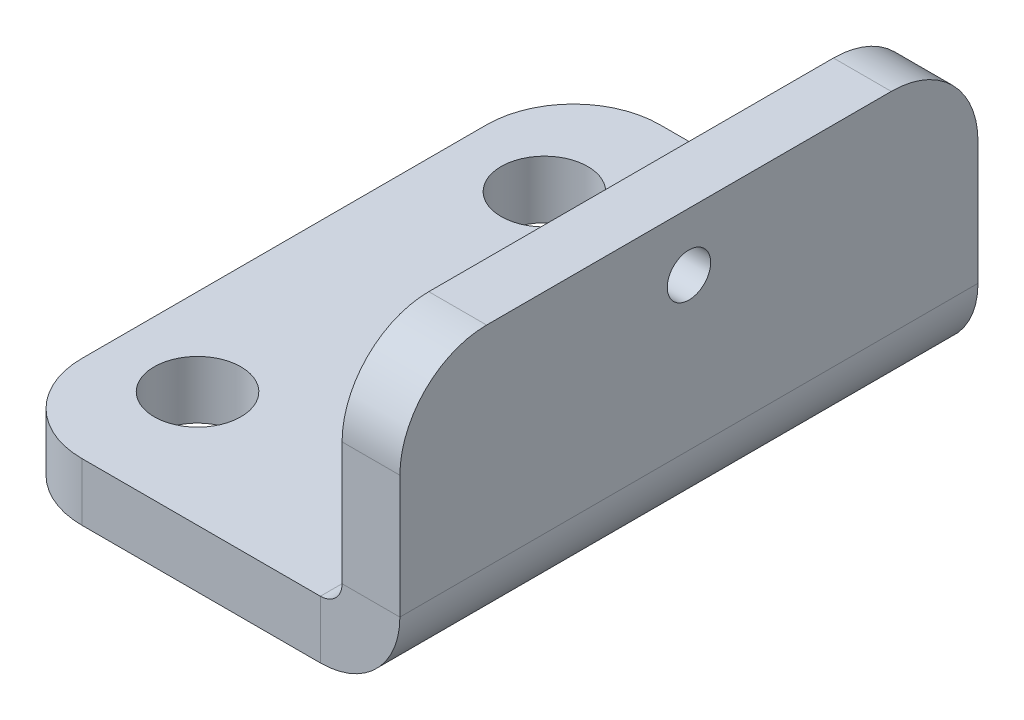
SolidWorks part; units mm, degrees
note: The reader was unsure of these and kept them because the rebuilt part matched: bend radius of "BaseBend1".
ref_plane "Front Plane" through (0, 0, 0) normal (0, 0, 1) x (1, 0, 0)
ref_plane "Top Plane" through (0, 0, 0) normal (0, 1, 0) x (1, 0, 0)
ref_plane "Right Plane" through (0, 0, 0) normal (1, 0, 0) x (0, 0, -1)
sketch "Sketch1" plane through (0, 0, 0) normal (0, 0, 1) x (1, 0, 0)
  line L0 (-12, 0) -> (0, 0)
  line L1 (0, 0) -> (0, 8)
  dimension "D1" = 8
  dimension "D2" = 12
base flange "Base-Flange1" sketch "Sketch1" end condition mid plane depth 20 reverse direction no thickness 2 reverse thickness direction no bend radius 0.75
bend "BaseBend1" bend radius 0.75 bend angle 90 parameters "D5"=1
fillet "Fillet1" radius 3 4 edges at (-12, -1, -10) (-12, -1, 10) (1, 8, -10) (1, 8, 10)
sketch "Sketch6" plane through (0, 0, 0) normal (0, 1, 0) x (1, 0, 0)
  line L0 (-12, -7) -> (-12, 7) construction
  line L1 (0, 0) -> (-12, 0) construction
  circle A0 centre (-9, 6) radius 1.5
  circle A1 centre (-9, -6) radius 1.5
  dimension "D2" = 3
  dimension "D1" = 3
  dimension "D3" = 6
extrude "Cut-Extrude1" cut sketch "Sketch6" against normal through all normal cut yes
sketch "Sketch7" plane through (0, 0, 0) normal (-1, 0, 0) x (0, 0, 1)
  line L0 (0, 0) -> (0, 8) construction
  line L1 (7, 8) -> (-7, 8) construction
  circle A0 centre (0, 6) radius 0.75
  dimension "D1" = 1.5
  dimension "D2" = 2
extrude "Cut-Extrude2" cut sketch "Sketch7" against normal through all normal cut yes
sketch "Bend-Lines1" [suppressed] plane through (0, 0, 0) normal (0, 1, 0) x (1, 0, 0)
sketch "Bounding-Box1" [suppressed] plane through (0, 0, 0) normal (0, 1, 0) x (1, 0, 0)
sheet metal parameters "Sheet-Metal1" thickness 2 parameters "D1"=0.75
flat pattern "Flat-Pattern1" [suppressed]
sketch "Bend-Lines2" plane through (0, 0, 0) normal (0, 1, 0) x (1, 0, 0)
  line L0 (0.436, 10) -> (0.436, -10) construction
  line L1 (0.436, 10) -> (0.436, -10) construction
sketch3d "Bounding-Box2" [suppressed]
  line L0 (0, 0, 0) -> (20.8719, 0, 0) construction
  line L1 (0, 20, 0) -> (20.8719, 20, 0) construction
  line L2 (0, 0, 0) -> (0, 20, 0) construction
  line L3 (20.8719, 0, 0) -> (20.8719, 20, 0) construction
bend of the flat pattern "Flatten-<BaseBend1>1"
sheet metal parameters "Sheet-Metal2" thickness 2 parameters "D1"=0.75
flat pattern "Flat-Pattern1"
sketch "Bend-Lines2" plane through (0, 0, 0) normal (0, 1, 0) x (1, 0, 0)
  line L0 (0.436, 10) -> (0.436, -10) construction
  line L1 (0.436, 10) -> (0.436, -10) construction
sketch3d "Bounding-Box2" [suppressed]
  line L0 (0, 0, 0) -> (20.8719, 0, 0) construction
  line L1 (0, 20, 0) -> (20.8719, 20, 0) construction
  line L2 (0, 0, 0) -> (0, 20, 0) construction
  line L3 (20.8719, 0, 0) -> (20.8719, 20, 0) construction
bend of the flat pattern "Flatten-<BaseBend1>1"
sheet metal parameters "Sheet-Metal3" thickness 2 parameters "D1"=0.75
flat pattern "Flat-Pattern1"
sketch "Bend-Lines2" plane through (0, 0, 0) normal (0, 1, 0) x (1, 0, 0)
  line L0 (0.436, 10) -> (0.436, -10) construction
  line L1 (0.436, 10) -> (0.436, -10) construction
sketch3d "Bounding-Box2" [suppressed]
  line L0 (0, 0, 0) -> (20.8719, 0, 0) construction
  line L1 (0, 20, 0) -> (20.8719, 20, 0) construction
  line L2 (0, 0, 0) -> (0, 20, 0) construction
  line L3 (20.8719, 0, 0) -> (20.8719, 20, 0) construction
bend of the flat pattern "Flatten-<BaseBend1>1"
